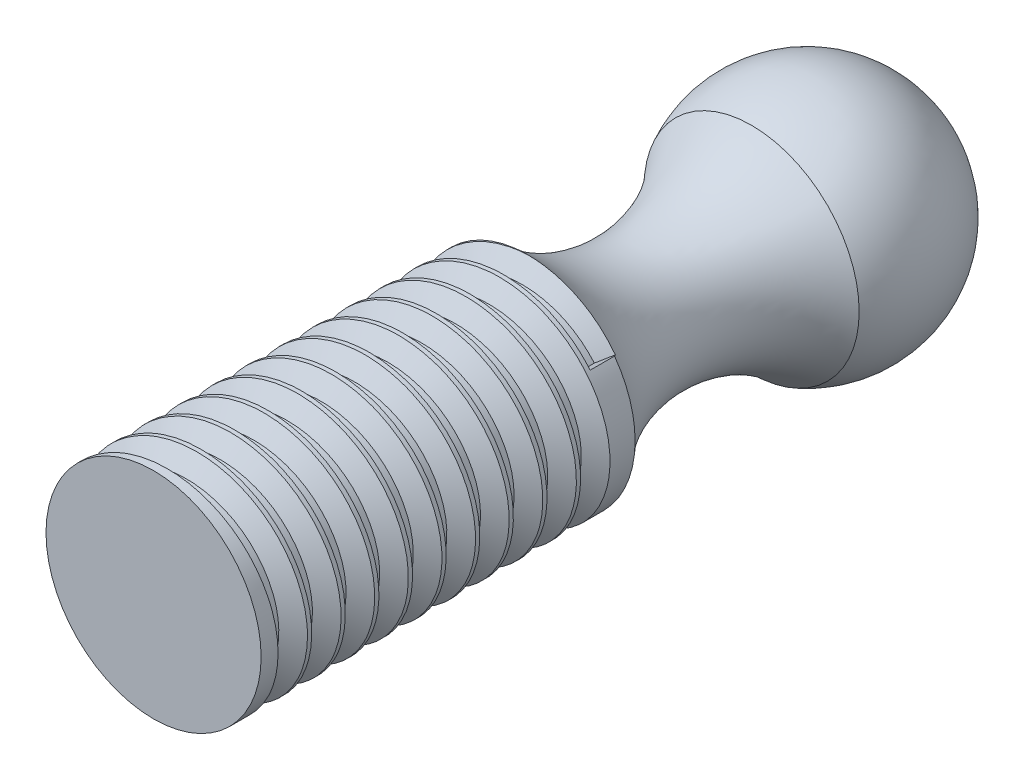
SolidWorks part; units mm, degrees
ref_plane "Piano frontale" through (0, 0, 0) normal (0, 0, 1) x (1, 0, 0)
ref_plane "Piano superiore" through (0, 0, 0) normal (0, 1, 0) x (1, 0, 0)
ref_plane "Piano destro" through (0, 0, 0) normal (1, 0, 0) x (0, 0, -1)
sketch "Schizzo2" plane through (0, 0, 0) normal (0, 0, 1) x (1, 0, 0)
  line L0 (13.398, -1.3546) -> (22.398, -1.3546)
  arc A0 (22.398, -1.3546) -> (13.398, -1.3546) centre (17.898, -1.3546) ccw
  dimension "D1" = 9
revolve "Rivoluzione1" add sketch "Schizzo2" angle 360 about L0
sketch "Schizzo3" plane through (0, 0, 0) normal (0, 0, 1) x (1, 0, 0)
  circle A0 centre (17.898, -1.3546) radius 4
  dimension "D1" = 8
extrude "Estrusione-Estrusione1" add sketch "Schizzo3" along normal blind 24.3
thread "Filettatura1" pitch 1.25 method cut profile "Profilo filettatura1" start angle 360, offset 0, length 13, pitch 1.25, diameter 8
ref_plane "Piano1" through (13.898, -1.3546, 24.3) normal (0, -1, 0) x (-1, 0, 0)
sketch "Profilo filettatura1" plane through (13.898, -1.3546, 24.3) normal (0, -1, 0) x (-1, 0, 0)
  line L0 (0, 0) -> (0, 1.25) construction
  line L11 (0, 0) -> (0, 1.0937)
  line L12 (0, 1.0937) -> (-0.6766, 0.7031)
  line L13 (-0.6766, 0.7031) -> (-0.6766, 0.3906)
  line L15 (-0.6766, 0.3906) -> (0, 0)
  line L17 (-0.6766, 0.5469) -> (0, 0.5469) construction
  point P2 (0, 0)
  dimension "Pitch" = 1.25
  dimension "Profile_Angle" = 60
  dimension "Profile_Land" = 0.3125
  dimension "Profile_Height" = 0.6766
sketch "Schizzo4" plane through (0, 0, 24.3) normal (0, 0, 1) x (1, 0, 0)
  circle A0 centre (17.8873, -1.3452) radius 4.0142
ref_axis "Assi1" through (17.898, -1.3546, 24.3) along (0, 0, -1)
ref_plane "Piano2" through (17.898, 0, 0) normal (1, 0, 0) x (0, 0, -1)
sketch "Schizzo6" plane through (17.898, 0, 0) normal (1, 0, 0) x (0, 0, -1)
  line L0 (-2.0616, 2.6454) -> (-10.3938, 2.6454) construction
  line L1 (-2.0616, 2.6454) -> (-10.3938, 2.6454)
  arc A0 (-2.0616, 2.6454) -> (-10.3938, 2.6454) centre (-6.2277, 6.9632) cw
  dimension "D1" = 6
revolve "Taglia-Rivoluzione4" cut sketch "Schizzo6" angle 360 about axis through (17.898, -1.3546, 24.3) along (0, 0, -1)
